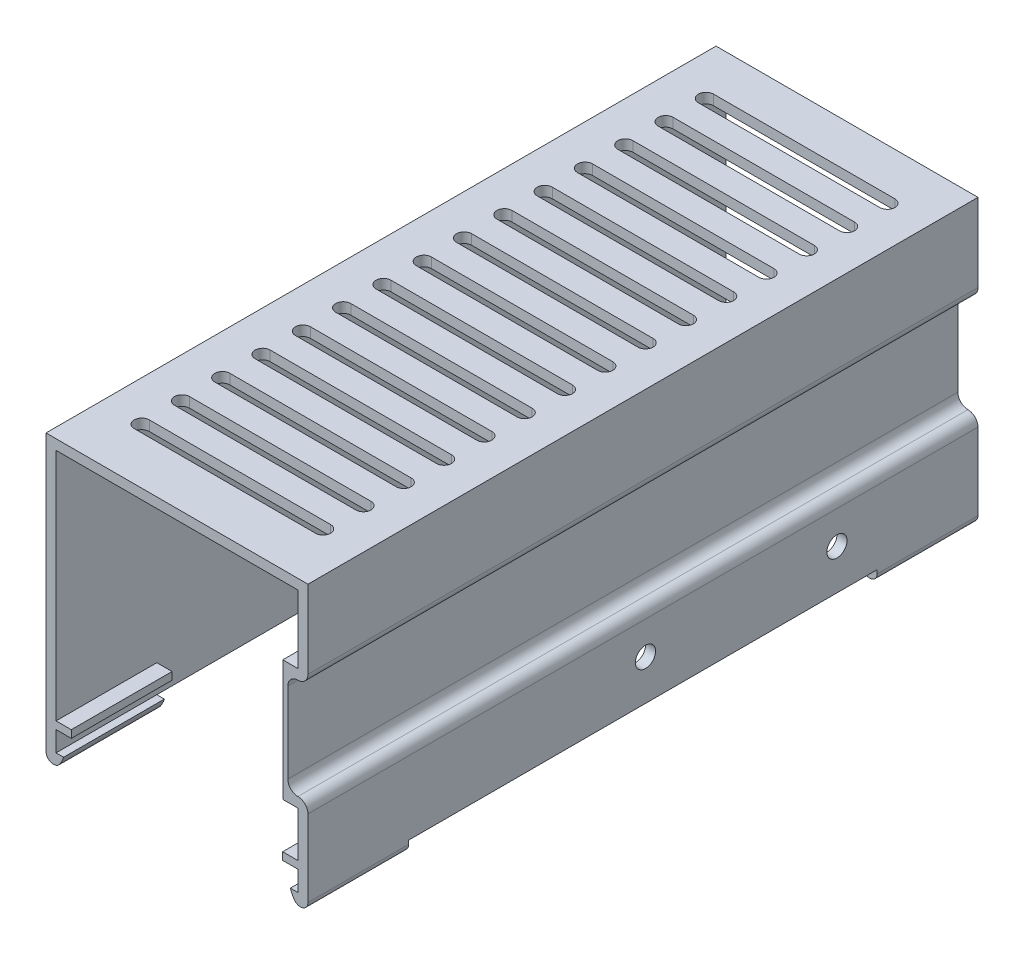
SolidWorks part; units mm, degrees
material "ABS"
ref_plane "Front Plane" through (0, 0, 0) normal (0, 0, 1) x (1, 0, 0)
ref_plane "Top Plane" through (0, 0, 0) normal (0, 1, 0) x (1, 0, 0)
ref_plane "Right Plane" through (0, 0, 0) normal (1, 0, 0) x (0, 0, -1)
sketch "Sketch1" plane through (0, 0, 0) normal (0, 0, 1) x (1, 0, 0)
  line L0 (0, 0) -> (0, 54)
  line L1 (0, 54) -> (52, 54)
  line L2 (52, 54) -> (52, 36.5)
  line L3 (52, 0) -> (50, 0)
  line L4 (50, 0) -> (50, 14.5)
  line L5 (50, 52) -> (2, 52)
  line L6 (2, 52) -> (2, 0)
  line L7 (2, 0) -> (0, 0)
  line L8 (50, 38.5) -> (47, 38.5)
  line L9 (47, 38.5) -> (47, 14.5)
  line L10 (47, 14.5) -> (50, 14.5)
  line L11 (52, 36.5) -> (48, 36.5)
  line L12 (48, 36.5) -> (48, 16.5)
  line L13 (48, 16.5) -> (52, 16.5)
  line L14 (50, 38.5) -> (50, 52)
  line L15 (52, 16.5) -> (52, 0)
  point P15 (48.5, 14.5)
  point P18 (48.5, 38.5)
  dimension "D1" = 2
  dimension "D2" = 2
  dimension "D3" = 2
  dimension "D4" = 48
  dimension "D5" = 54
  dimension "D6" = 2
  dimension "D7" = 2
  dimension "D8" = 1
  dimension "D9" = 20
  dimension "D10" = 13.5
  dimension "D11" = 2
extrude "Boss-Extrude1" add sketch "Sketch1" along normal blind 133
sketch "Sketch2" plane through (52, 0, 0) normal (1, 0, 0) x (0, 0, -1)
  line L0 (0, 36.5) -> (0, 54) construction
  line L1 (-133, 0) -> (0, 0) construction
  line L2 (-133, 36.5) -> (-133, 54) construction
  circle A0 centre (-131, 1.5) radius 1
  circle A1 centre (-2, 1.5) radius 1
  dimension "D1" = 2
  dimension "D2" = 2
  dimension "D3" = 2
  dimension "D4" = 1.5
  dimension "D5" = 1.5
  dimension "D6" = 2
extrude "Cut-Extrude1" [suppressed] cut sketch "Sketch2" against normal up to surface (2 mm away)
hole_wizard "M2 Clearance Hole1" [suppressed] positions "Sketch4" profile "Sketch5" hole size "M2" standard "ISO"
sketch "Sketch4" plane through (52, 0, 0) normal (1, 0, 0) x (0, 0, -1)
  line L0 (-10, 0) -> (0, 0) construction
  line L1 (-10, 0) -> (-10, 53) construction
  point P0 (-8, 1.5)
  dimension "D1" = 1.5
  dimension "D2" = 2
sketch "Sketch5" plane through (52, 1.5, 8) normal (0, 1, 0) x (0, 0, -1)
  line L0 (0, 0) -> (0, 50.72)
  line L1 (0, 50.72) -> (1.2, 49.999)
  line L2 (1.2, 49.999) -> (1.2, 0)
  line L5 (1.2, 0) -> (0, 0)
  line L10 (0, 50.72) -> (-1.2, 49.999) construction
  line L11 (0, -6.35) -> (0, 107.95) construction
  dimension "Hole Dia." = 2.4
  dimension "Hole Depth" = 49.999
  dimension "Drill Angle" = 118
ref_plane "Plane1" through (0, 0, 66.5) normal (0, 0, 1) x (1, 0, 0)
mirror "Mirror1" [suppressed] about plane through (0, 0, 66.5) normal (0, 0, 1)
ref_plane "Plane2" through (26, 0, 0) normal (1, 0, 0) x (0, 0, -1)
mirror "Mirror2" [suppressed] about plane through (26, 0, 0) normal (1, 0, 0)
sketch "Sketch6" plane through (0, 0, 0) normal (-1, 0, 0) x (0, 0, 1)
  line L0 (17.6879, 18.1495) -> (104.9806, 18.1495) construction
  text T0 "WAXO" font "Century Gothic" height in points 72
extrude "Cut-Extrude2" cut sketch "Sketch6" against normal blind 1.5
sketch "Sketch7" plane through (0, 54, 0) normal (0, 1, 0) x (1, 0, 0)
  line L0 (8, -10) -> (44, -10) construction
  line L1 (8, -8.5) -> (44, -8.5)
  line L2 (8, -11.5) -> (44, -11.5)
  line L3 (0, -133) -> (0, 0) construction
  line L4 (52, -133) -> (52, 0) construction
  line L5 (52, 0) -> (0, 0) construction
  arc A0 (8, -8.5) -> (8, -11.5) centre (8, -10) ccw
  arc A1 (44, -11.5) -> (44, -8.5) centre (44, -10) ccw
  point P2 (26, -10)
  dimension "D4" = 10
  dimension "D1" = 8
  dimension "D2" = 8
  dimension "D3" = 3
extrude "Cut-Extrude3" cut sketch "Sketch7" against normal up to surface (2 mm away) up to face at (26, 52, 66.5)
pattern_linear "LPattern1" count 15 spacing 8 along (0, 0, 1) of "Cut-Extrude3"
sketch "Sketch8" plane through (52, 0, 0) normal (1, 0, 0) x (0, 0, -1)
  line L0 (-133, 36.5) -> (-133, 54) construction
  line L1 (-133, 37.5) -> (-130, 37.5)
  line L2 (-133, 37.5) -> (-133, 17.5)
  line L3 (-133, 17.5) -> (-130, 17.5)
  line L4 (-130, 37.5) -> (-130, 17.5)
  line L5 (-133, 54) -> (0, 54) construction
  dimension "D1" = 20
  dimension "D2" = 16.5
  dimension "D3" = 3
extrude "Cut-Extrude4" [suppressed] cut sketch "Sketch8" against normal up to surface (2 mm away)
fillet "Fillet1" [suppressed] radius 1.5
fillet "Fillet2" radius 2 4 edges at (48, 16.5, 66.5) (48, 36.5, 66.5) (52, 36.5, 66.5) (52, 16.5, 66.5)
sketch "Sketch9" plane through (0, 0, 133) normal (0, 0, 1) x (1, 0, 0)
  line L0 (52, 0) -> (48.5, 0)
  line L1 (52, 0) -> (52, -4)
  line L2 (50, 14.5) -> (50, 0) construction
  arc A0 (48.5, 0) -> (52, -4) centre (55.0522, 2.2019) ccw
  dimension "D1" = 1.5
  dimension "D2" = 4
extrude "Boss-Extrude2" add sketch "Sketch9" against normal blind 20
mirror "Mirror3" about plane through (0, 0, 66.5) normal (0, 0, 1) of "Boss-Extrude2"
mirror "Mirror4" about plane through (26, 0, 0) normal (1, 0, 0) of "Mirror3", "Boss-Extrude2"
fillet "Fillet3" radius 1.5 4 edges at (52, -4, 123) (52, -4, 10) (0, -4, 10) (0, -4, 123)
sketch "Sketch10" plane through (50, 0, 0) normal (-1, 0, 0) x (0, 0, 1)
  line L0 (0, 14.5) -> (0, 0) construction
  line L1 (0, 4) -> (20, 4)
  line L2 (0, 4) -> (0, 5.5)
  line L3 (0, 5.5) -> (20, 5.5)
  line L4 (20, 4) -> (20, 5.5)
  line L5 (20, 0) -> (0, 0) construction
  dimension "D1" = 20
  dimension "D2" = 4
  dimension "D3" = 1.5
extrude "Boss-Extrude3" add sketch "Sketch10" along normal blind 3.0205
mirror "Mirror5" about plane through (0, 0, 66.5) normal (0, 0, 1) of "Boss-Extrude3"
mirror "Mirror6" about plane through (26, 0, 0) normal (1, 0, 0) of "Mirror5", "Boss-Extrude3"
sketch "Sketch11" plane through (0, 0, 0) normal (-1, 0, 0) x (0, 0, 1)
  line L0 (113, 0) -> (20, 0) construction
  line L1 (0, 54) -> (0, 0) construction
  circle A0 centre (28, 8) radius 2
  circle A1 centre (66, 8) radius 2
  point P6 (0, 0)
  dimension "D1" = 4
  dimension "D2" = 4
  dimension "D3" = 8
  dimension "D4" = 38
  dimension "D5" = 28
extrude "Cut-Extrude5" cut sketch "Sketch11" against normal through all
equation "\"D2@Sketch2\"=\"D1@Sketch2\""
equation "\"D2@Sketch11\"=\"D1@Sketch11\""
